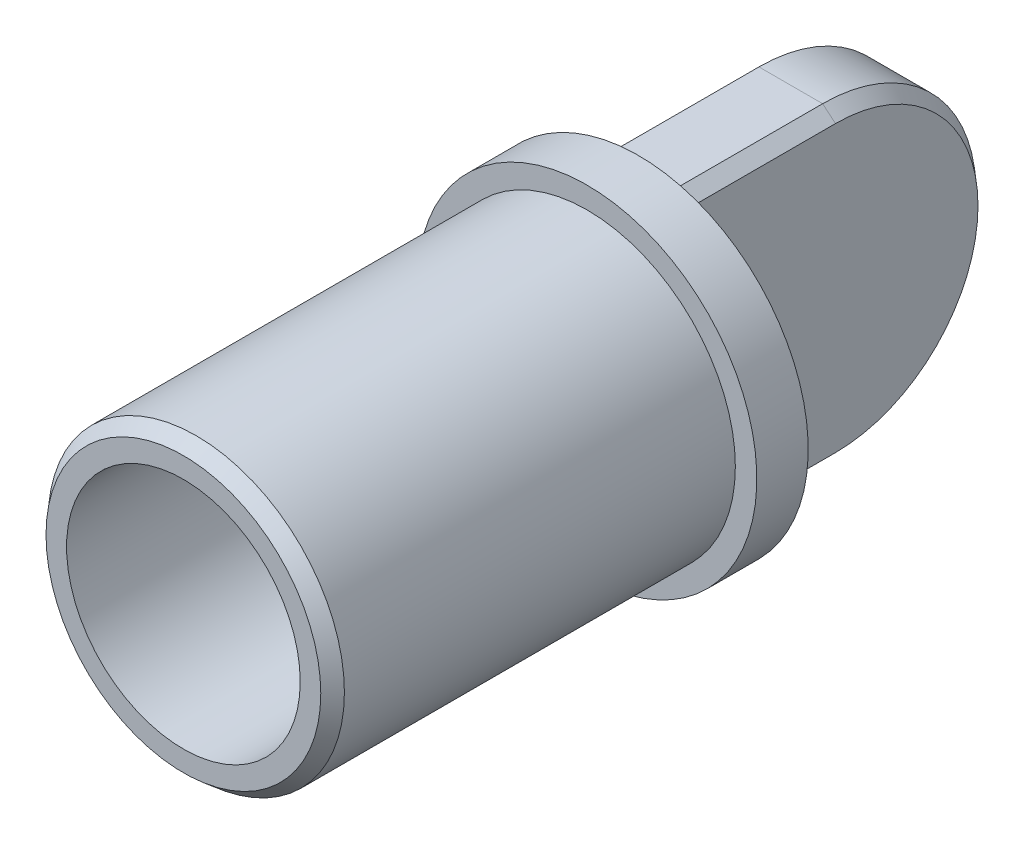
SolidWorks part; units mm, degrees
note: The reader was unsure of these and kept them because the rebuilt part matched: shared geometry of "Sketch2<5>".
ref_plane "Front Plane" through (0, 0, 0) normal (0, 0, 1) x (1, 0, 0)
ref_plane "Top Plane" through (0, 0, 0) normal (0, 1, 0) x (1, 0, 0)
ref_plane "Right Plane" through (0, 0, 0) normal (1, 0, 0) x (0, 0, -1)
sketch "Sketch1" plane through (0, 0, 0) normal (0, 0, 1) x (1, 0, 0)
  circle A1 centre (0, 0) radius 7.3259
  dimension "D1" = 14.6518
extrude "Extrude1" add sketch "Sketch1" along normal blind 30.083
sketch "Sketch2" plane through (0, 0, 0) normal (1, 0, 0) x (0, 0, -1)
  line L0 (0, 7.5786) -> (-7.5786, 7.5786)
  line L1 (-7.5786, 7.5786) -> (-7.5786, -7.5786)
  line L2 (-7.5786, -7.5786) -> (0, -7.5786)
  circle A0 centre (0, 0) radius 7.5786
extrude "Extrude4" cut sketch "Sketch2" against normal through all and the other way through all contours A0 | A0 L0 L1 | A0 L1 L2
extrude "Extrude5" add sketch "Sketch2<5>" along normal mid plane 4.318 contours A0 L0 L1 | A0 | A0 L1 L2
sketch "Sketch2<5>" plane through (0, 0, 0) normal (1, 0, 0) x (0, 0, -1) same geometry as "Sketch2"
sketch "Sketch3" plane through (0, 0, 7.5786) normal (0, 0, -1) x (-1, 0, 0)
  circle A0 centre (0, 0) radius 8.3882
extrude "Extrude6" add sketch "Sketch3" against normal blind 2.54
chamfer "Chamfer1" distance 0.635 angle 40 6 edges at (-2.159, -7.5786, 3.7893) (-2.159, 0, -7.5786) (-2.159, 7.5786, 3.7893) (2.159, -7.5786, 3.7893) (2.159, 0, -7.5786) (2.159, 7.5786, 3.7893)
chamfer "Chamfer2" distance 0.635 angle 40 1 edges at (7.3259, 0, 30.083)
sketch "Sketch4" plane through (0, 0, 30.083) normal (0, 0, 1) x (1, 0, 0)
  circle A0 centre (0, 0) radius 5.7767
extrude "Extrude7" cut sketch "Sketch4" against normal up to surface (19.9644 mm away) up to face at (-8.3882, 0, 10.1186)
